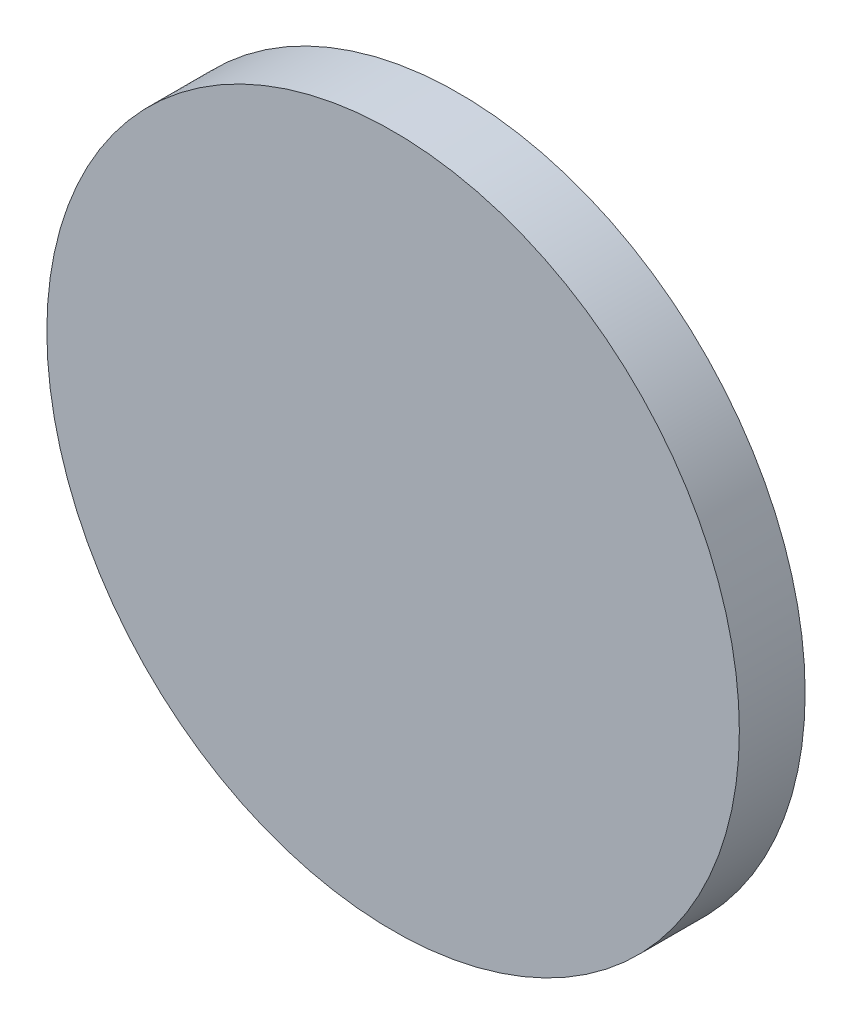
SolidWorks part; units mm, degrees
ref_plane "Front Plane" through (0, 0, 0) normal (0, 0, 1) x (1, 0, 0)
ref_plane "Top Plane" through (0, 0, 0) normal (0, 1, 0) x (1, 0, 0)
ref_plane "Right Plane" through (0, 0, 0) normal (1, 0, 0) x (0, 0, -1)
sketch "Sketch1" plane through (0, 0, 0) normal (0, 0, 1) x (1, 0, 0)
  circle A0 centre (0, 0) radius 20.05
  circle A1 centre (0, 0) radius 21.05
  dimension "D1" = 40.1
  dimension "D2" = 1
extrude "Boss-Extrude1" add sketch "Sketch1" along normal blind 3
sketch "Sketch2" plane through (0, 0, 3) normal (0, 0, 1) x (1, 0, 0)
  circle A0 centre (0, 0) radius 21.05
  circle A1 centre (0, 0) radius 21.05 construction
  point P8 (0, 0)
  circle M3 centre (0, 0) radius 21.05
  circle M4 centre (0, 0) radius 20.05
extrude "Boss-Extrude3" add sketch "Sketch2" along normal blind 1 contours M3 M4 | M4 region at (-20.4546, 0, 3) region at (0, 0, 3)
fillet "Fillet1" radius 0.5 1 edges at (20.05, 0, 0)
